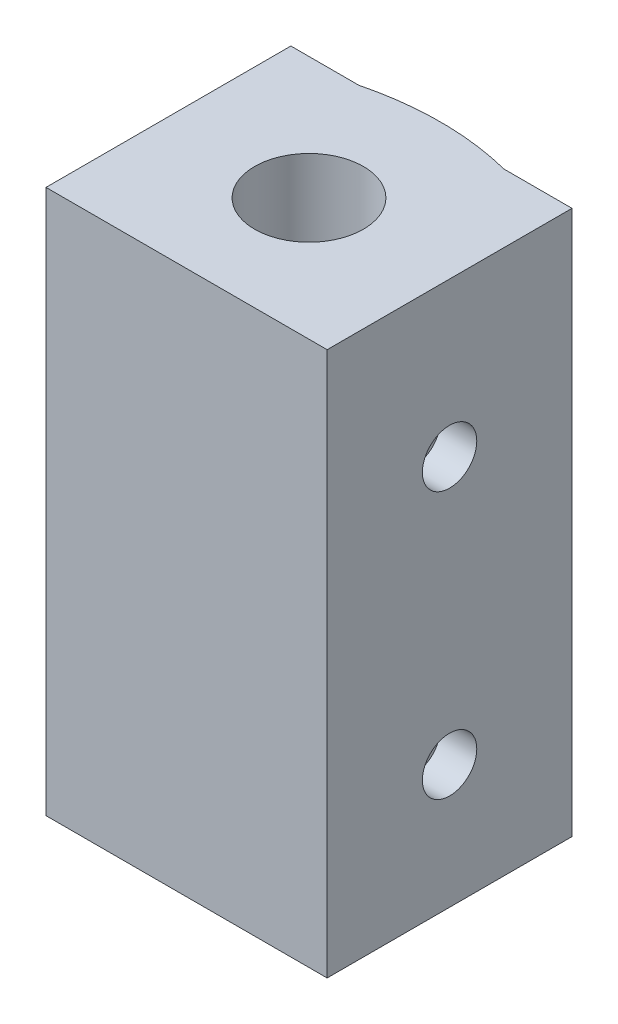
SolidWorks part; units mm, degrees
ref_plane "Front Plane" through (0, 0, 0) normal (0, 0, 1) x (1, 0, 0)
ref_plane "Top Plane" through (0, 0, 0) normal (0, 1, 0) x (1, 0, 0)
ref_plane "Right Plane" through (0, 0, 0) normal (1, 0, 0) x (0, 0, -1)
sketch "Sketch1" plane through (0, 0, 0) normal (0, 1, 0) x (1, 0, 0)
  line L0 (7.75, 0) -> (7.75, -2.25) construction
  line L1 (0, 0) -> (15.5, 0)
  line L2 (0, 0) -> (0, 13.5)
  line L3 (0, 13.5) -> (3.75, 13.5)
  line L4 (15.5, 0) -> (15.5, 13.5)
  line L5 (11.75, 13.5) -> (15.5, 13.5)
  arc A0 (3.75, 13.5) -> (11.75, 13.5) centre (7.75, -2.25) cw
  point P8 (7.75, 14)
  dimension "D1" = 15.5
  dimension "D2" = 13.5
  dimension "D3" = 14
  dimension "D4" = 8
extrude "Boss-Extrude1" add sketch "Sketch1" along normal blind 30
sketch "Sketch2" plane through (0, 30, 0) normal (0, 1, 0) x (1, 0, 0)
  line L0 (0, 6.75) -> (7.75, 6.75) construction
  line L1 (0, 13.5) -> (0, 0) construction
  line L2 (7.75, 0) -> (7.75, 6.75) construction
  line L3 (0, 0) -> (15.5, 0) construction
  circle A0 centre (7.75, 6.75) radius 3
  dimension "D1" = 6
extrude "Cut-Extrude1" cut sketch "Sketch2" against normal offset from surface (18 mm away) 18 up to face at (7.75, 30, -9.0833)
sketch "Sketch3" plane through (0, 12, 0) normal (0, 1, 0) x (1, 0, 0)
  circle A0 centre (7.75, 6.75) radius 1.75
  circle A1 centre (7.75, 6.75) radius 3 construction
  dimension "D1" = 3.5
extrude "Cut-Extrude2" cut sketch "Sketch3" against normal through all
sketch "Sketch4" plane through (15.5, 0, 0) normal (1, 0, 0) x (0, 0, -1)
  line L2 (6.75, 30) -> (6.75, 0) construction
  line L3 (0, 30) -> (13.5, 30) construction
  line L4 (0, 0) -> (13.5, 0) construction
  circle A0 centre (6.75, 21.515) radius 1.5
  circle A1 centre (6.75, 6.815) radius 1.5
  point P10 (0, 0)
  point P11 (0, 0)
  dimension "D1" = 3
  dimension "D2" = 6.815
  dimension "D3" = 14.7
extrude "Cut-Extrude3" cut sketch "Sketch4" against normal blind 2
